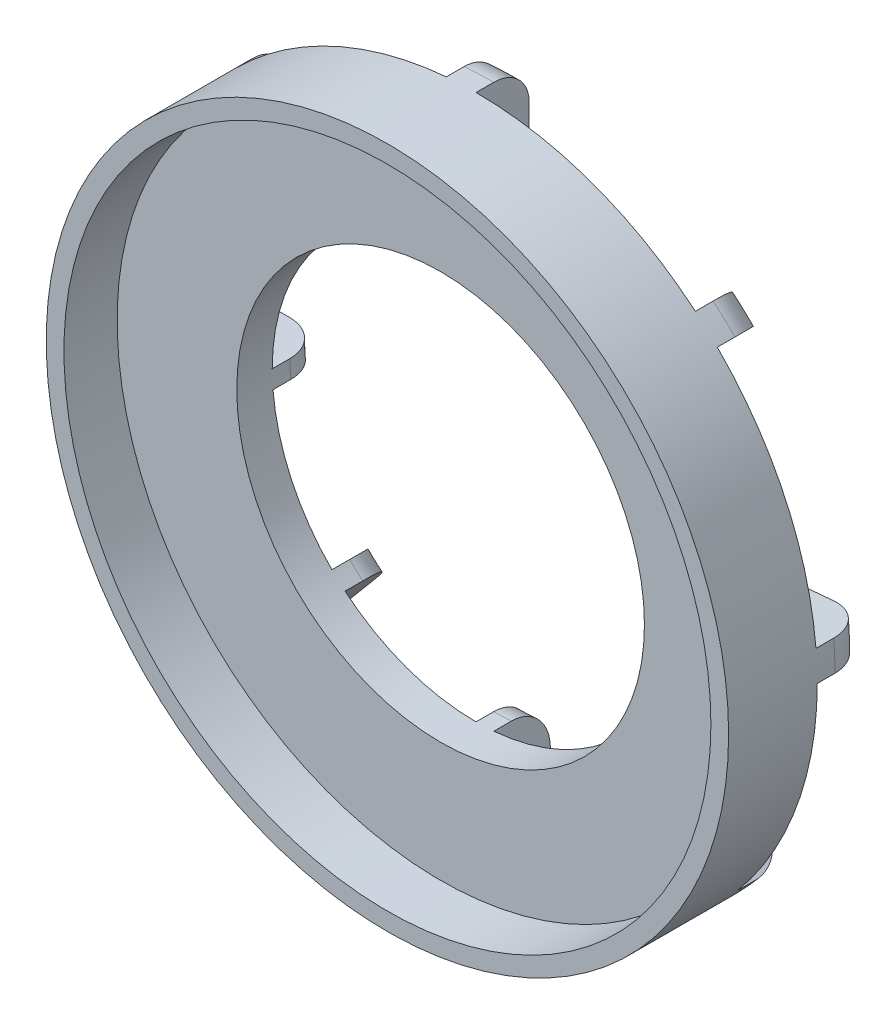
SolidWorks part; units mm, degrees
ref_plane "Front Plane" through (0, 0, 0) normal (0, 0, 1) x (1, 0, 0)
ref_plane "Top Plane" through (0, 0, 0) normal (0, 1, 0) x (1, 0, 0)
ref_plane "Right Plane" through (0, 0, 0) normal (1, 0, 0) x (0, 0, -1)
sketch "Sketch1" plane through (0, 0, 0) normal (0, 0, 1) x (1, 0, 0)
  circle A0 centre (0, 0) radius 18.25
  circle A1 centre (0, 0) radius 11.5
  circle A2 centre (0, 0) radius 19.25
  dimension "D1" = 36.5
  dimension "D2" = 23
  dimension "D3" = 1
extrude "Boss-Extrude1" add sketch "Sketch1" along normal blind 2 contours A0 A1 region at (-17.7338, 0, 0)
extrude "Boss-Extrude2" add sketch "Sketch1<4>" along normal blind 5 contours A2 A0 region at (-18.7055, 0, 0)
sketch "Sketch1<4>" plane through (0, 0, 0) normal (0, 0, 1) x (1, 0, 0) same geometry as "Sketch1"
sketch "Sketch2" plane through (0, 0, 0) normal (0, 0, -1) x (-1, 0, 0)
  line L0 (0, 19.25) -> (0, 11.5)
  line L1 (1.0023, 11.4562) -> (1.6777, 19.1767)
  line L2 (0, 0) -> (1.6777, 19.1767) construction
  line L3 (0, 0) -> (0, 19.25) construction
  circle A1 centre (0, 0) radius 19.25 construction
  arc A2 (0, 11.5) -> (1.0023, 11.4562) centre (0, 0) cw
  circle A3 centre (0, 0) radius 11.5 construction
  arc A4 (1.6777, 19.1767) -> (0, 19.25) centre (0, 0) ccw
  circle M7 centre (0, 0) radius 11.5
  circle M8 centre (0, 0) radius 19.25
  dimension "D1" = 5
extrude "Boss-Extrude3" add sketch "Sketch2" along normal blind 3 contours L1 L0 M7 M8 region at (-0.6846, 15.6806, 0)
fillet "Fillet2" radius 2 2 edges at (-0.8397, 19.2317, -3) (-0.5016, 11.4891, -3)
ref_axis "Axis1" through (0, 0, 5.4) along (0, 0, -1)
pattern_circular "CirPattern1" count 8 every 45 about axis through (0, 0, 5.4) along (0, 0, -1) of "Boss-Extrude3", "Fillet2"
